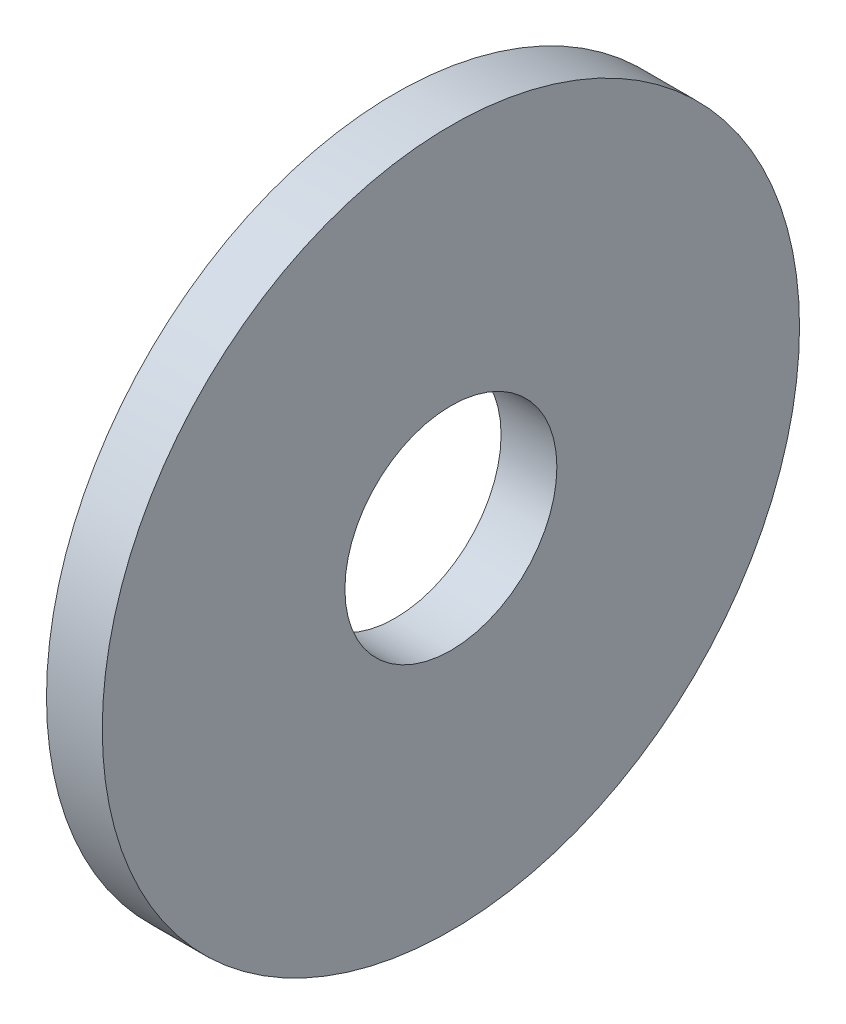
SolidWorks part; units mm, degrees
ref_plane "Front" through (0, 0, 0) normal (0, 0, 1) x (1, 0, 0)
ref_plane "Top" through (0, 0, 0) normal (0, 1, 0) x (1, 0, 0)
ref_plane "Right" through (0, 0, 0) normal (1, 0, 0) x (0, 0, -1)
ref_plane "Plane1" through (0, 0, 0) normal (0, 0, -1) x (-1, 0, 0)
sketch "Sketch1" plane through (0, 0, 0) normal (0, 0, -1) x (-1, 0, 0)
  line L0 (-1.778, 3.3782) -> (0, 3.3782)
  line L1 (0, 3.3782) -> (0, 11.1125)
  line L2 (0, 11.1125) -> (-1.778, 11.1125)
  line L3 (-1.778, 11.1125) -> (-1.778, 3.3782)
  line L4 (-1.778, 0) -> (0, 0) construction
revolve "Revolve1" add sketch "Sketch1" angle 360 about L4 reverse direction yes
